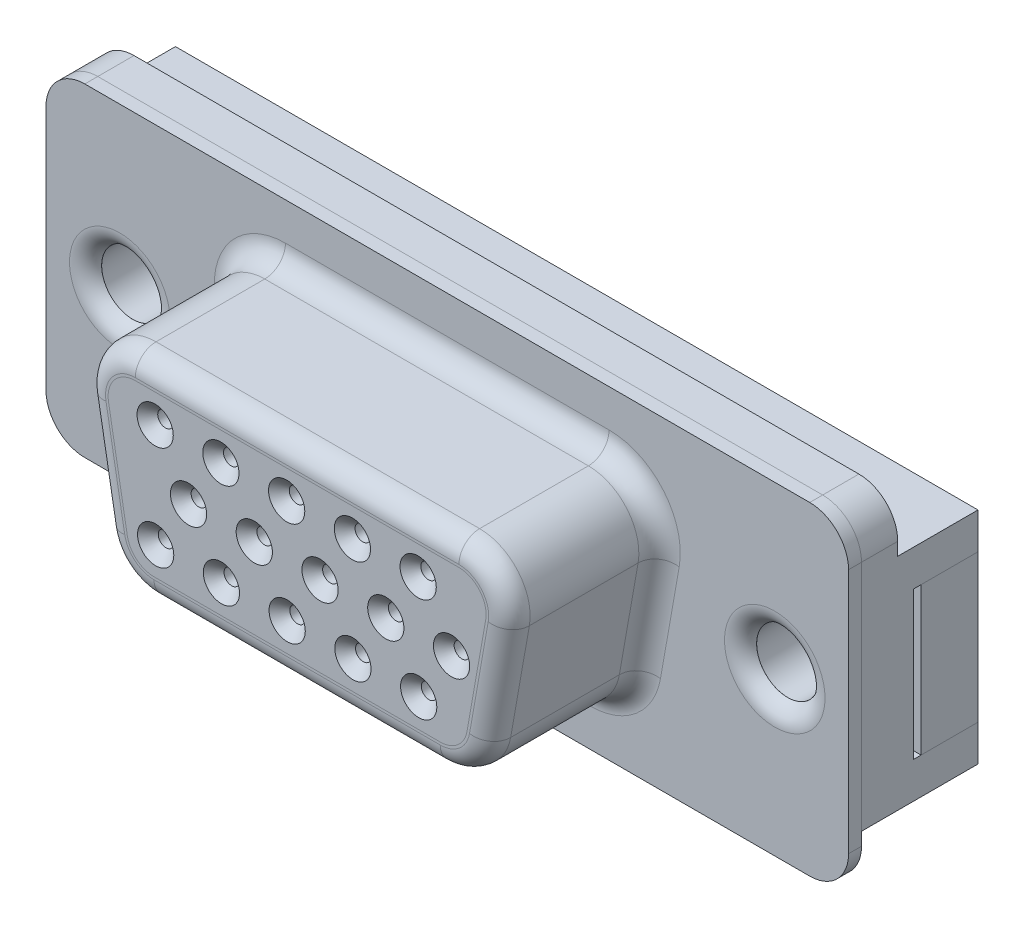
SolidWorks part; units mm, degrees
material "Duranickel(R) 301"
ref_plane "Alzado" through (0, 0, 0) normal (0, 0, 1) x (1, 0, 0)
ref_plane "Planta" through (0, 0, 0) normal (0, 1, 0) x (1, 0, 0)
ref_plane "Vista lateral" through (0, 0, 0) normal (1, 0, 0) x (0, 0, -1)
sketch "Croquis1" plane through (0, 0, 0) normal (0, 0, 1) x (1, 0, 0)
  line L1 (-15.5, 6.25) -> (15.5, 6.25)
  line L2 (-15.5, 6.25) -> (-15.5, -6.25)
  line L3 (-15.5, -6.25) -> (15.5, -6.25)
  line L4 (15.5, 6.25) -> (15.5, -6.25)
  dimension "D1" = 31
  dimension "D2" = 12.5
  dimension "D3" = 15.5
  dimension "D4" = 6.25
extrude "Extruir1" add sketch "Croquis1" along normal blind 0.5
fillet "Redondeo1" radius 1.5 4 edges at (15.5, -6.25, 0.25) (-15.5, -6.25, 0.25) (-15.5, 6.25, 0.25) (15.5, 6.25, 0.25)
sketch "Croquis2" plane through (0, 0, 0.5) normal (0, 0, 1) x (1, 0, 0)
  line L0 (0, -6.25) -> (0, -8.8787) construction
  line L1 (-6.25, 4) -> (6.25, 4)
  line L2 (-8.2, 2.05) -> (-8.2, -4) construction
  line L3 (-5.5271, -4) -> (5.5271, -4)
  line L4 (8.2, 4) -> (8.2, -4) construction
  line L5 (-14, -6.25) -> (14, -6.25) construction
  line L6 (15.5, 0) -> (12.8437, 0) construction
  line L7 (15.5, -4.75) -> (15.5, 4.75) construction
  line L8 (-6.25, 2.05) -> (-5.5271, -2.05) construction
  line L9 (6.25, 2.05) -> (5.5271, -2.05) construction
  line L10 (-8.1704, 1.7114) -> (-7.4474, -2.3886)
  line L11 (8.1704, 1.7114) -> (7.4474, -2.3886)
  arc A0 (-6.25, 4) -> (-8.1704, 1.7114) centre (-6.25, 2.05) ccw
  arc A1 (8.1704, 1.7114) -> (6.25, 4) centre (6.25, 2.05) ccw
  arc A2 (-7.4474, -2.3886) -> (-5.5271, -4) centre (-5.5271, -2.05) ccw
  arc A3 (5.5271, -4) -> (7.4474, -2.3886) centre (5.5271, -2.05) ccw
  dimension "D5" = 3.9
  dimension "D6" = 3.9
  dimension "D7" = 3.9
  dimension "D8" = 3.9
  dimension "D9" = 10
  dimension "D2" = 8
  dimension "D3" = 8.2
  dimension "D4" = 4
  dimension "D10" = 10
  dimension "D11" = 8.2
extrude "Extruir2" add sketch "Croquis2" along normal blind 5.8
sketch "Croquis3" plane through (0, 0, 6.3) normal (0, 0, 1) x (1, 0, 0)
  line L0 (-5.5271, -3.1) -> (5.5271, -3.1)
  line L1 (6.5611, -2.2323) -> (7.284, 1.8677)
  line L2 (6.25, 3.1) -> (-6.25, 3.1)
  line L3 (-7.284, 1.8677) -> (-6.5611, -2.2323)
  line L4 (-5.5271, -4) -> (5.5271, -4)
  line L5 (7.4474, -2.3886) -> (8.1704, 1.7114)
  line L6 (6.25, 4) -> (-6.25, 4)
  line L7 (-8.1704, 1.7114) -> (-7.4474, -2.3886)
  line L8 (-5.5271, -4) -> (5.5271, -4) construction
  line L9 (7.4474, -2.3886) -> (8.1704, 1.7114) construction
  line L10 (6.25, 4) -> (-6.25, 4) construction
  line L11 (-8.1704, 1.7114) -> (-7.4474, -2.3886) construction
  arc A0 (5.5271, -3.1) -> (6.5611, -2.2323) centre (5.5271, -2.05) ccw
  arc A1 (7.284, 1.8677) -> (6.25, 3.1) centre (6.25, 2.05) ccw
  arc A2 (-6.25, 3.1) -> (-7.284, 1.8677) centre (-6.25, 2.05) ccw
  arc A3 (-6.5611, -2.2323) -> (-5.5271, -3.1) centre (-5.5271, -2.05) ccw
  arc A4 (-7.4474, -2.3886) -> (-5.5271, -4) centre (-5.5271, -2.05) ccw
  arc A5 (5.5271, -4) -> (7.4474, -2.3886) centre (5.5271, -2.05) ccw
  arc A6 (8.1704, 1.7114) -> (6.25, 4) centre (6.25, 2.05) ccw
  arc A7 (-6.25, 4) -> (-8.1704, 1.7114) centre (-6.25, 2.05) ccw
  arc A8 (-7.4474, -2.3886) -> (-5.5271, -4) centre (-5.5271, -2.05) ccw construction
  arc A9 (5.5271, -4) -> (7.4474, -2.3886) centre (5.5271, -2.05) ccw construction
  arc A10 (8.1704, 1.7114) -> (6.25, 4) centre (6.25, 2.05) ccw construction
  arc A11 (-6.25, 4) -> (-8.1704, 1.7114) centre (-6.25, 2.05) ccw construction
  dimension "D1" = 0
  dimension "D2" = 0.9
extrude "Cortar-Extruir1" cut sketch "Croquis3" against normal blind 9.8
fillet "Redondeo2" radius 0.8 8 edges at (7.7438, 3.3034, 6.3) (7.8089, -0.3386, 6.3) (6.7805, -3.5438, 6.3) (0, -4, 6.3) (-6.7805, -3.5438, 6.3) (-7.8089, -0.3386, 6.3) (-7.7438, 3.3034, 6.3) (0, 4, 6.3)
fillet "Redondeo3" radius 0.8 8 edges at (7.7438, 3.3034, 0.5) (7.8089, -0.3386, 0.5) (6.7805, -3.5438, 0.5) (0, -4, 0.5) (-6.7805, -3.5438, 0.5) (-7.8089, -0.3386, 0.5) (-7.7438, 3.3034, 0.5) (0, 4, 0.5)
sketch "Croquis4" plane through (0, 0, 0.5) normal (0, 0, 1) x (1, 0, 0)
  line L0 (14, 6.25) -> (-14, 6.25) construction
  circle A0 centre (12.65, 0) radius 1.2
  circle A1 centre (-12.65, 0) radius 1.2
  point P4 (0, 6.25)
  dimension "D1" = 2.4
  dimension "D2" = 2.4
  dimension "D3" = 25.3
  dimension "D4" = 12.65
  dimension "D5" = 6.25
extrude "Cortar-Extruir2" cut sketch "Croquis4" against normal blind 9.8
fillet "Redondeo4" radius 0.8 2 edges at (-11.45, 0, 0.5) (13.85, 0, 0.5)
sketch "Croquis5" plane through (0, 0, 0) normal (0, 0, -1) x (-1, 0, 0)
  line L0 (-14, 6.25) -> (14, 6.25) construction
  line L1 (-14, 6.25) -> (14, 6.25)
  line L2 (-15.5, -4.25) -> (15.5, -4.25)
  line L3 (15.5, 4.75) -> (15.5, -4.25)
  line L4 (15.5, 4.75) -> (15.5, -4.75) construction
  line L5 (-15.5, 4.75) -> (-15.5, -4.25)
  arc A0 (15.5, 4.75) -> (14, 6.25) centre (14, 4.75) ccw construction
  arc A1 (-14, 6.25) -> (-15.5, 4.75) centre (-14, 4.75) ccw construction
  arc A2 (15.5, 4.75) -> (14, 6.25) centre (14, 4.75) ccw
  arc A3 (-14, 6.25) -> (-15.5, 4.75) centre (-14, 4.75) ccw
  dimension "D1" = 10.5
extrude "Extruir3" add sketch "Croquis5" along normal blind 4.5 separate body
sketch "Croquis6" plane through (15.5, 0, 0) normal (1, 0, 0) x (0, 0, -1)
  line L0 (-0.5, 6.25) -> (-0.5, 4.75) construction
  line L1 (1.4, 7.3662) -> (5.4944, 7.3662)
  line L2 (1.4, 7.3662) -> (1.4, 4.25)
  line L3 (1.4, 4.25) -> (5.4944, 4.25)
  line L4 (5.4944, 7.3662) -> (5.4944, 4.25)
  line L5 (4.5, 6.25) -> (0, 6.25) construction
  dimension "D1" = 1.9
  dimension "D2" = 2
extrude "Cortar-Extruir3" cut sketch "Croquis6" against normal blind 36.5
sketch "Croquis7" plane through (0, 0, -4.5) normal (0, 0, -1) x (-1, 0, 0)
  line L0 (-15.5, 4.25) -> (-15.5, -4.25) construction
  line L1 (-15.5, 2.85) -> (-9.8, 2.85)
  line L2 (-15.5, 2.85) -> (-15.5, -2.85)
  line L3 (-15.5, -2.85) -> (-9.8, -2.85)
  line L4 (-9.8, 2.85) -> (-9.8, -2.85)
  line L5 (0, 6.25) -> (0, 11.7053) construction
  line L6 (-14, 6.25) -> (14, 6.25) construction
  line L7 (9.8, 2.85) -> (9.8, -2.85)
  line L8 (15.5, -2.85) -> (9.8, -2.85)
  line L9 (15.5, 2.85) -> (15.5, -2.85)
  line L10 (15.5, 2.85) -> (9.8, 2.85)
  circle A0 centre (-12.65, 0) radius 1.2 construction
  dimension "D2" = 2.85
  dimension "D1" = 5.7
  dimension "D3" = 5.7
extrude "Cortar-Extruir4" cut sketch "Croquis7" against normal blind 2.5
sketch "Croquis8" plane through (0, 0, -2) normal (0, 0, -1) x (-1, 0, 0)
  circle A0 centre (-12.65, 0) radius 1.2
  circle A1 centre (12.65, 0) radius 1.2
extrude "Cortar-Extruir5" cut sketch "Croquis8" against normal blind 2.5
sketch "Croquis9" plane through (0, 0, 0) normal (0, 0, 1) x (1, 0, 0)
  line L0 (6.5611, -2.2323) -> (7.284, 1.8677) construction
  line L1 (-5.5271, -3.1) -> (5.5271, -3.1) construction
  line L2 (-7.284, 1.8677) -> (-6.5611, -2.2323) construction
  line L3 (6.25, 3.1) -> (-6.25, 3.1) construction
  line L4 (6.5611, -2.2323) -> (7.284, 1.8677)
  line L5 (-5.5271, -3.1) -> (5.5271, -3.1)
  line L6 (-7.284, 1.8677) -> (-6.5611, -2.2323)
  line L7 (6.25, 3.1) -> (-6.25, 3.1)
  arc A0 (7.284, 1.8677) -> (6.25, 3.1) centre (6.25, 2.05) ccw construction
  arc A1 (5.5271, -3.1) -> (6.5611, -2.2323) centre (5.5271, -2.05) ccw construction
  arc A2 (-6.5611, -2.2323) -> (-5.5271, -3.1) centre (-5.5271, -2.05) ccw construction
  arc A3 (-6.25, 3.1) -> (-7.284, 1.8677) centre (-6.25, 2.05) ccw construction
  arc A4 (7.284, 1.8677) -> (6.25, 3.1) centre (6.25, 2.05) ccw
  arc A5 (5.5271, -3.1) -> (6.5611, -2.2323) centre (5.5271, -2.05) ccw
  arc A6 (-6.5611, -2.2323) -> (-5.5271, -3.1) centre (-5.5271, -2.05) ccw
  arc A7 (-6.25, 3.1) -> (-7.284, 1.8677) centre (-6.25, 2.05) ccw
extrude "Extruir4" add sketch "Croquis9" along normal blind 6.3 separate body
sketch "Croquis10" plane through (0, 0, 6.3) normal (0, 0, 1) x (1, 0, 0)
  circle A0 centre (-5.484, 2) radius 0.3
  circle A1 centre (-2.944, 2) radius 0.3
  circle A2 centre (-0.404, 2) radius 0.3
  circle A3 centre (2.136, 2) radius 0.3
  circle A4 centre (4.676, 2) radius 0.3
  circle A5 centre (4.6958, -2) radius 0.3
  circle A6 centre (2.1558, -2) radius 0.3
  circle A7 centre (-0.3842, -2) radius 0.3
  circle A8 centre (-2.9242, -2) radius 0.3
  circle A9 centre (-5.4642, -2) radius 0.3
  circle A10 centre (0.8858, 0) radius 0.3
  circle A11 centre (3.4258, 0) radius 0.3
  circle A12 centre (5.9658, 0) radius 0.3
  circle A13 centre (-1.6542, 0) radius 0.3
  circle A14 centre (-4.1942, 0) radius 0.3
  dimension "D2" = 0.6
  dimension "D1" = 2
  dimension "D3" = 1.8
extrude "Cortar-Extruir6" cut sketch "Croquis10" against normal blind 9.3
chamfer "Chaflán1" distance 0.4 angle 45 15 edges at (4.9958, -2, 6.3) (6.2658, 0, 6.3) (4.976, 2, 6.3) (2.436, 2, 6.3) (3.7258, 0, 6.3) (2.4558, -2, 6.3) (-0.0842, -2, 6.3) (1.1858, 0, 6.3) (-0.104, 2, 6.3) (-1.3542, 0, 6.3) (-2.6242, -2, 6.3) (-5.1642, -2, 6.3) (-3.8942, 0, 6.3) (-2.644, 2, 6.3) (-5.184, 2, 6.3)
combine bodies "Combinar1" operation type add bodies to combine 111 110
sketch "Croquis11" plane through (0, 0, -4.5) normal (0, 0, -1) x (-1, 0, 0)
  line L1 (-9.8, 2.85) -> (-15.5, 2.85)
  line L2 (-9.8, 2.85) -> (-9.8, -2.85)
  line L3 (-9.8, -2.85) -> (-15.5, -2.85)
  line L4 (-15.5, 2.85) -> (-15.5, -2.85)
  line L5 (9.8, 2.85) -> (15.5, 2.85)
  line L6 (9.8, 2.85) -> (9.8, -2.85)
  line L7 (9.8, -2.85) -> (15.5, -2.85)
  line L8 (15.5, 2.85) -> (15.5, -2.85)
  circle A0 centre (-12.65, 0) radius 1.2
  circle A1 centre (12.65, 0) radius 1.2
extrude "Extruir5" add sketch "Croquis11" against normal blind 2.2 separate body
